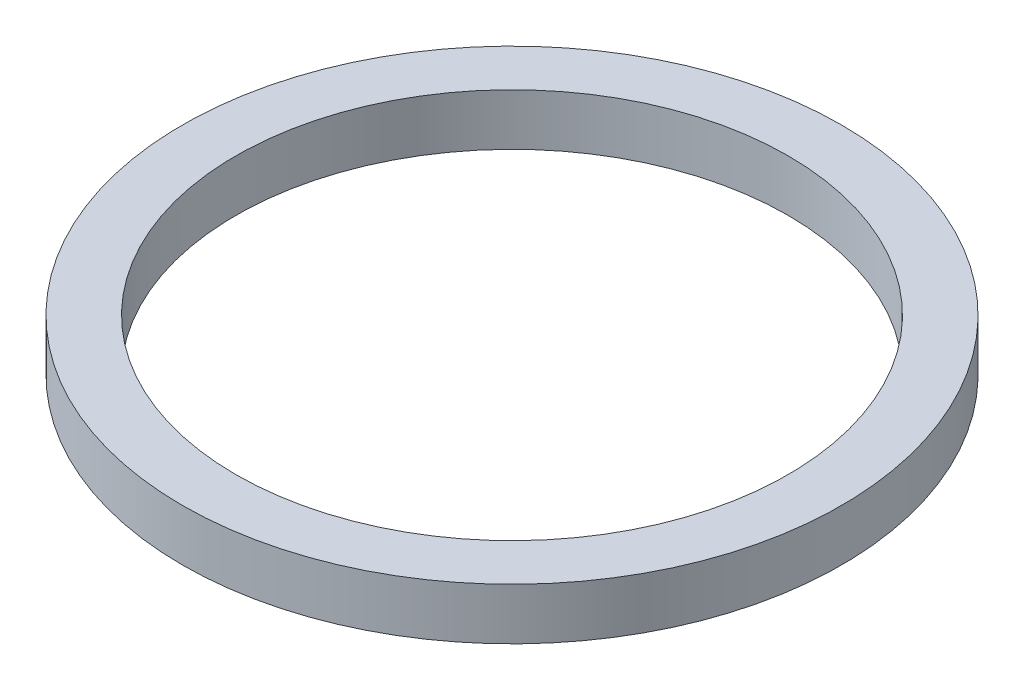
SolidWorks part; units mm, degrees
ref_plane "Front Plane" through (0, 0, 0) normal (0, 0, 1) x (1, 0, 0)
ref_plane "Top Plane" through (0, 0, 0) normal (0, 1, 0) x (1, 0, 0)
ref_plane "Right Plane" through (0, 0, 0) normal (1, 0, 0) x (0, 0, -1)
sketch "Sketch1" plane through (0, 0, 0) normal (0, 1, 0) x (1, 0, 0)
  circle A0 centre (0, 0) radius 16.05
  circle A1 centre (0, 0) radius 19.155
  dimension "D1" = 32.1
  dimension "D2" = 38.31
extrude "Boss-Extrude1" add sketch "Sketch1" along normal blind 3
